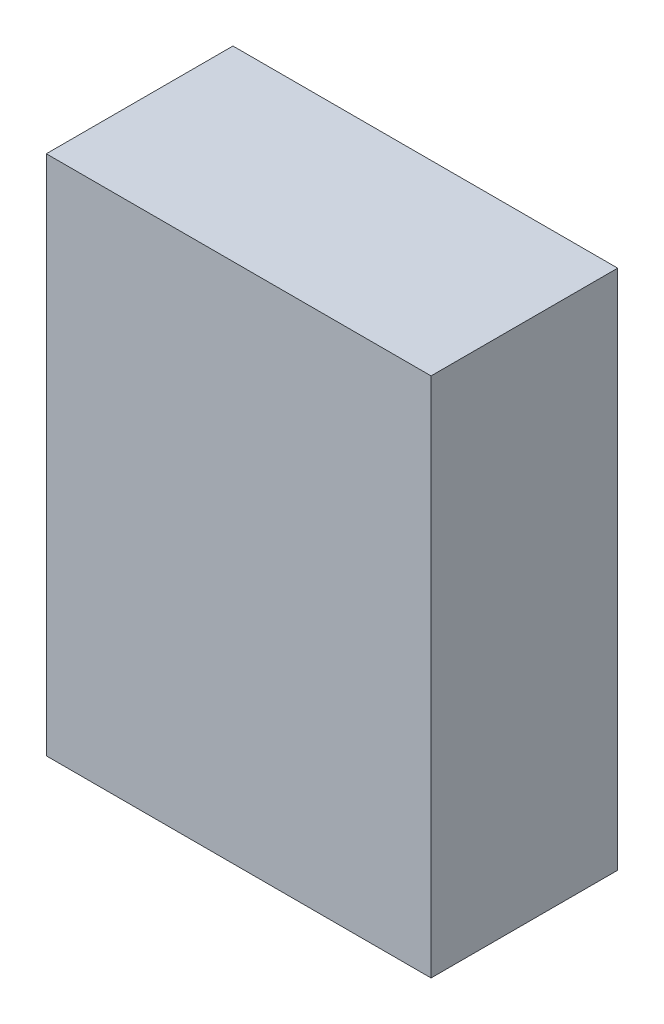
SolidWorks part; units mm, degrees
ref_plane "Ebene vorne" through (0, 0, 0) normal (0, 0, 1) x (1, 0, 0)
ref_plane "Ebene oben" through (0, 0, 0) normal (0, 1, 0) x (1, 0, 0)
ref_plane "Ebene rechts" through (0, 0, 0) normal (1, 0, 0) x (0, 0, -1)
sketch "Skizze1" plane through (0, 0, 0) normal (0, 0, 1) x (1, 0, 0)
  line L1 (0, 0) -> (20.6158, 0)
  line L2 (0, 0) -> (0, -27.9399)
  line L3 (0, -27.9399) -> (20.6158, -27.9399)
  line L4 (20.6158, 0) -> (20.6158, -27.9399)
extrude "Aufsatz-Linear austragen1" add sketch "Skizze1" along normal blind 10
